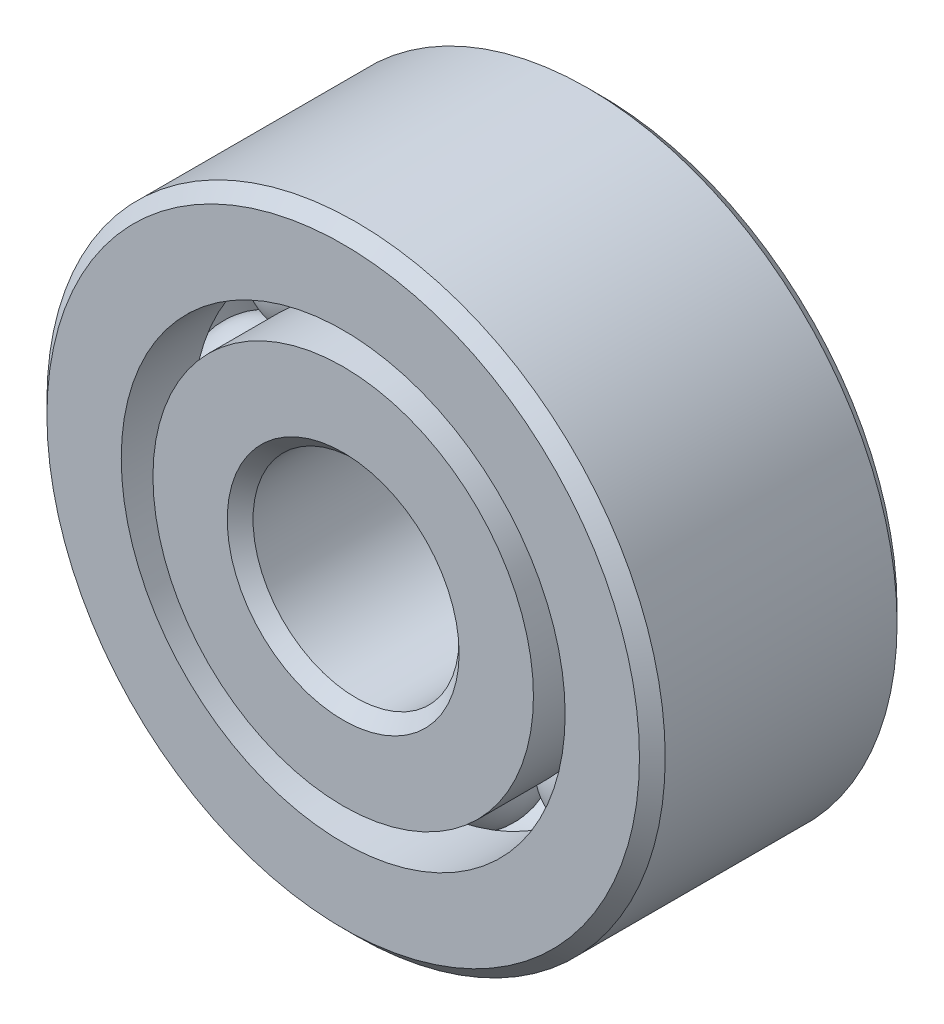
SolidWorks part; units mm, degrees
ref_plane "Front Plane" through (0, 0, 0) normal (0, 0, 1) x (1, 0, 0)
ref_plane "Top Plane" through (0, 0, 0) normal (0, 1, 0) x (1, 0, 0)
ref_plane "Right Plane" through (0, 0, 0) normal (1, 0, 0) x (0, 0, -1)
sketch "Sketch1" plane through (0, 0, 0) normal (1, 0, 0) x (0, 0, -1)
  line L0 (-1.9844, 0) -> (1.9844, 0) construction
  line L1 (0, 4.7625) -> (0, -4.7625) construction
  line L2 (1.7859, 4.7625) -> (-1.7859, 4.7625)
  line L3 (-1.7859, 4.7625) -> (-1.9844, 4.5641)
  line L4 (-1.9844, 4.5641) -> (-1.9844, 3.4192)
  line L5 (-1.9844, 3.4192) -> (-0.8819, 3.4192)
  line L6 (1.9844, 3.4192) -> (0.8819, 3.4192)
  line L7 (1.9844, 4.5641) -> (1.9844, 3.4192)
  line L8 (1.7859, 4.7625) -> (1.9844, 4.5641)
  line L9 (0, 4.7625) -> (0, 3.175) construction
  line L10 (0, 3.175) -> (0, 1.5875) construction
  arc A0 (-0.8819, 3.4192) -> (0.8819, 3.4192) centre (0, 3.175) cw
  point P14 (0, 1.5875)
  dimension "D3" = 1.7639
  dimension "D1" = 45
  dimension "Width" = 3.9688
  dimension "OD" = 9.525
  dimension "D2" = 0.1984
  dimension "Shaft Dia" = 3.175
  dimension "D4" = 0.2442
revolve "Revolve1" add sketch "Sketch1" angle 360 about L0
sketch "Sketch3" plane through (0, 0, 0) normal (1, 0, 0) x (0, 0, -1)
  line L0 (-1.9844, 2.9308) -> (-0.8819, 2.9308)
  line L1 (0, 4.7625) -> (0, -4.7625) construction
  line L2 (-1.9844, 4.5641) -> (-1.9844, 3.4192) construction
  line L3 (-1.9844, 2.9308) -> (-1.9844, 1.7859)
  line L4 (-1.7859, 4.7625) -> (-1.9844, 4.5641) construction
  line L5 (-1.9844, 1.7859) -> (-1.7859, 1.5875)
  line L6 (-1.7859, 1.5875) -> (1.7859, 1.5875)
  line L7 (1.7859, 4.7625) -> (1.7859, -4.7625) construction
  line L8 (1.7859, 1.5875) -> (1.9844, 1.7859)
  line L9 (1.9844, -4.5641) -> (1.9844, 4.5641) construction
  line L10 (1.9844, 1.7859) -> (1.9844, 2.9308)
  line L11 (1.9844, 2.9308) -> (0.8819, 2.9308)
  line L13 (1.7859, 4.7625) -> (1.9844, 4.5641) construction
  arc A0 (0.8819, 3.4192) -> (-0.8819, 3.4192) centre (0, 3.175) ccw construction
  arc A1 (0.8819, 2.9308) -> (-0.8819, 2.9308) centre (0, 3.175) cw
revolve "Revolve3" add sketch "Sketch3" angle 360 about L0
sketch "Sketch4" plane through (0, 0, 0) normal (1, 0, 0) x (0, 0, -1)
  line L0 (-0.9151, 3.175) -> (0.9151, 3.175)
  arc A2 (-0.9151, 3.175) -> (0.9151, 3.175) centre (0, 3.175) cw
  arc A3 (0.8819, 3.4192) -> (-0.8819, 3.4192) centre (0, 3.175) ccw construction
revolve "Revolve4" add sketch "Sketch4" angle 360 about L0
ref_axis "Axis1" through (0, 0, -1.9844) along (0, 0, 1)
pattern_circular "CirPattern1" count 8 every 45 about axis through (0, 0, -1.9844) along (0, 0, 1) of bodies 104
sketch "Sketch5" plane through (0, 0, 0) normal (1, 0, 0) x (0, 0, -1)
  line L0 (-1.9844, 3.4192) -> (-0.8819, 3.4192) construction
  line L1 (-1.8852, 3.4192) -> (-0.9151, 3.4192)
  line L2 (-1.8852, 3.4192) -> (-1.8852, 2.9308)
  line L3 (-1.8852, 2.9308) -> (-0.9151, 2.9308)
  line L4 (-0.9151, 3.4192) -> (-0.9151, 2.9308)
  line L5 (-1.9844, 2.9308) -> (-0.8819, 2.9308) construction
  line L6 (1.9844, 3.4192) -> (0.8819, 3.4192) construction
  line L7 (1.8852, 3.4192) -> (0.9151, 3.4192)
  line L8 (1.8852, 3.4192) -> (1.8852, 2.9308)
  line L9 (1.8852, 2.9308) -> (0.9151, 2.9308)
  line L10 (0.9151, 3.4192) -> (0.9151, 2.9308)
  line L11 (1.9844, 2.9308) -> (0.8819, 2.9308) construction
  line L12 (-1.7859, 4.7625) -> (-1.9844, 4.5641) construction
  point P18 (-1.8852, 4.6633)
revolve "Revolve5" [suppressed] add sketch "Sketch5" angle 360 about L0
equation "\"D2@Sketch1\" = \"Width@Sketch1\"*.05"
equation "\"D3@Sketch1\" = \"Width@Sketch1\"/2.25"
equation "\"D4@Sketch1\" = (((\"OD@Sketch1\"-\"Width@Sketch1\")/2)/3.25)/3.5"
equation "\"D2@CirPattern1\" = 360/\"Balls@CirPattern1\""
